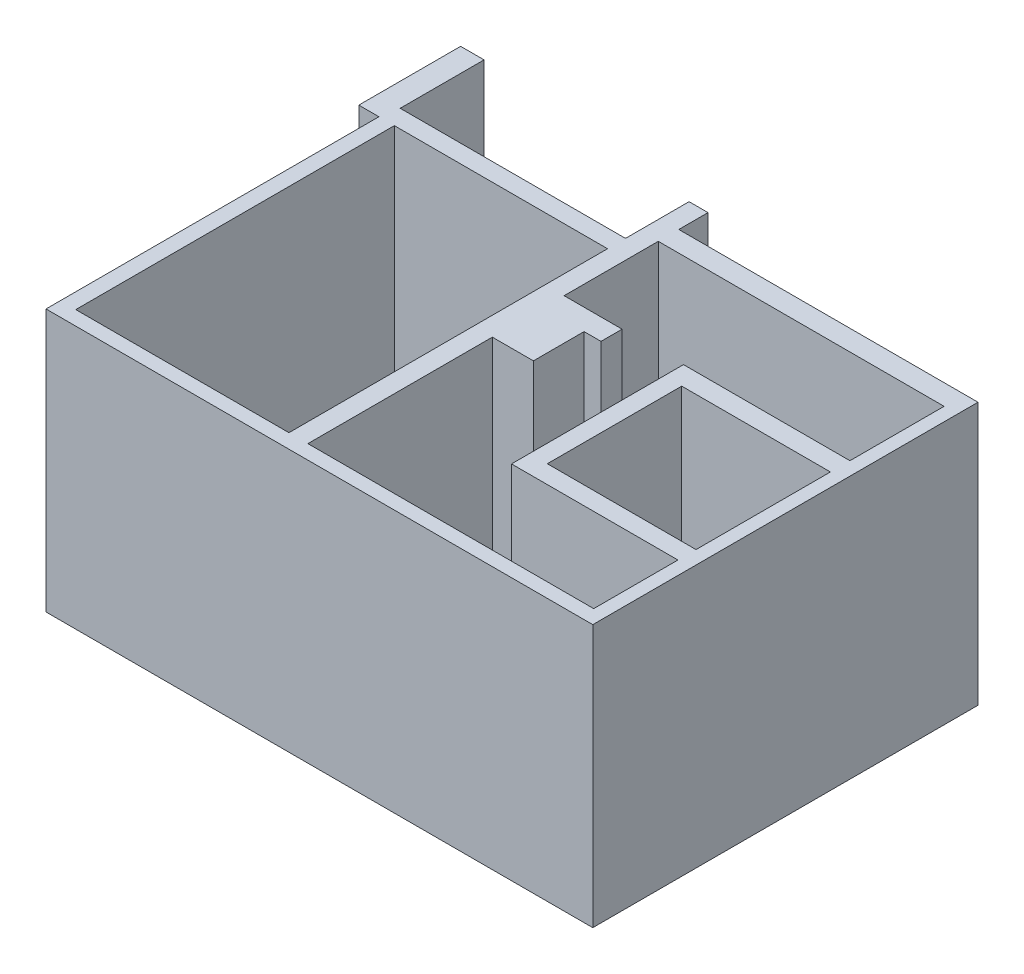
SolidWorks part; units mm, degrees
ref_plane "Спереди" through (0, 0, 0) normal (0, 0, 1) x (1, 0, 0)
ref_plane "Сверху" through (0, 0, 0) normal (0, 1, 0) x (1, 0, 0)
ref_plane "Справа" through (0, 0, 0) normal (1, 0, 0) x (0, 0, -1)
sketch "Эскиз1" plane through (0, 0, 0) normal (0, 1, 0) x (1, 0, 0)
  line L0 (-685.4426, 1097.0797) -> (-685.4426, 165.8934)
  line L1 (-685.4426, 165.8934) -> (-501.3311, 165.8934)
  line L2 (-501.3311, 165.8934) -> (-501.3311, -2878.4837)
  line L3 (-501.3311, -2878.4837) -> (4498.6689, -2878.4837)
  line L4 (4498.6689, -2878.4837) -> (4498.6689, 644.1483)
  line L5 (4498.6689, 644.1483) -> (1762.5932, 644.1483)
  line L6 (1762.5932, 644.1483) -> (1762.5932, 911.4083)
  line L7 (1762.5932, 911.4083) -> (1589.382, 911.4083)
  line L8 (1589.382, 911.4083) -> (1589.382, 330.0005)
  line L9 (1589.382, 330.0005) -> (-471.0768, 330.0005)
  line L10 (-471.0768, 330.0005) -> (-471.0768, 1097.0797)
  line L11 (-471.0768, 1097.0797) -> (-685.4426, 1097.0797)
  line L12 (-360.1773, 165.8934) -> (-360.1773, -2747.527)
  line L13 (-360.1773, -2747.527) -> (1589.382, -2747.527)
  line L14 (1589.382, -2747.527) -> (1589.382, 165.8934)
  line L15 (1589.382, 165.8934) -> (-360.1773, 165.8934)
  line L16 (1762.5932, 456.5973) -> (1762.5932, -404.5171)
  line L17 (1762.5932, -2747.527) -> (4376.3002, -2747.527)
  line L18 (4376.3002, -2747.527) -> (4376.3002, -1977.3333)
  line L19 (4376.3002, 456.5973) -> (1762.5932, 456.5973)
  line L20 (4376.3002, -1977.3333) -> (2854.2189, -1977.3333)
  line L21 (2854.2189, -1977.3333) -> (2854.2189, -404.5171)
  line L22 (2854.2189, -404.5171) -> (4376.3002, -404.5171)
  line L23 (4376.3002, -582.9666) -> (3016.5591, -582.9666)
  line L24 (3016.5591, -582.9666) -> (3016.5591, -1812.1171)
  line L25 (3016.5591, -1812.1171) -> (4376.3002, -1812.1171)
  line L26 (4376.3002, -404.5171) -> (4376.3002, 456.5973)
  line L27 (4376.3002, -1812.1171) -> (4376.3002, -582.9666)
  line L28 (1762.5932, -404.5171) -> (2292.905, -404.5171)
  line L29 (2292.905, -404.5171) -> (2292.905, -597.5774)
  line L30 (2292.905, -597.5774) -> (2138.1755, -597.5774)
  line L31 (2138.1755, -597.5774) -> (2138.1755, -1060.9221)
  line L32 (2138.1755, -1060.9221) -> (1762.5932, -1060.9221)
  line L33 (1762.5932, -1060.9221) -> (1762.5932, -2747.527)
  dimension "D1" = 5000
extrude "Бобышка-Вытянуть1" add sketch "Эскиз1" along normal blind 2400
